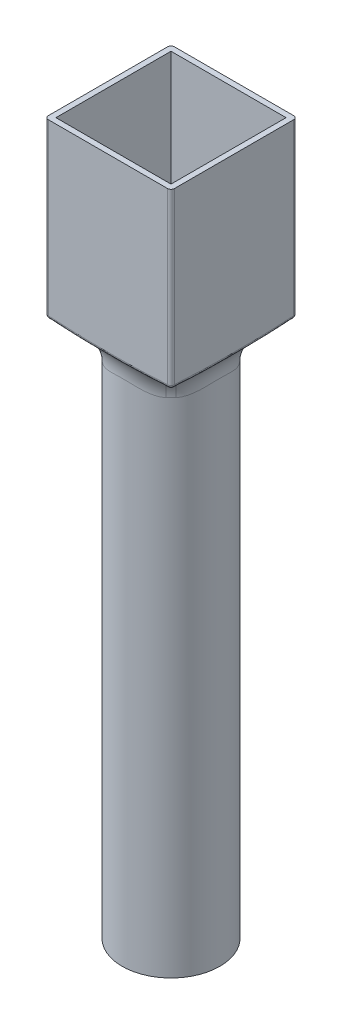
SolidWorks part; units mm, degrees
ref_plane "Спереди" through (0, 0, 0) normal (0, 0, 1) x (1, 0, 0)
ref_plane "Сверху" through (0, 0, 0) normal (0, 1, 0) x (1, 0, 0)
ref_plane "Справа" through (0, 0, 0) normal (1, 0, 0) x (0, 0, -1)
other "Configuration Table"
sketch "Эскиз1" plane through (0, 0, 0) normal (0, 1, 0) x (1, 0, 0)
  line L1 (-18.2, 18.2) -> (18.2, 18.2)
  line L2 (-18.2, 18.2) -> (-18.2, -18.2)
  line L3 (-18.2, -18.2) -> (18.2, -18.2)
  line L4 (18.2, 18.2) -> (18.2, -18.2)
  line L5 (0, -18.2) -> (0, 18.2) construction
  line L6 (-18.2, 0) -> (18.2, 0) construction
  line L7 (-16.6, 16.6) -> (16.6, 16.6)
  line L8 (-16.6, 16.6) -> (-16.6, -16.6)
  line L9 (-16.6, -16.6) -> (16.6, -16.6)
  line L10 (16.6, 16.6) -> (16.6, -16.6)
  line L11 (0, -16.6) -> (0, 16.6) construction
  line L12 (-16.6, 0) -> (16.6, 0) construction
  point P0 (0, 0)
  point P4 (0, 0)
  dimension "D1" = 36.4
  dimension "D2" = 33.2
extrude "Бобышка-Вытянуть1" add sketch "Эскиз1" along normal blind 48
sketch "Эскиз2" plane through (0, 0, 0) normal (0, -1, 0) x (1, 0, 0)
  line L1 (-18.2, -18.2) -> (18.2, -18.2)
  line L2 (-18.2, -18.2) -> (-18.2, 18.2)
  line L3 (-18.2, 18.2) -> (18.2, 18.2)
  line L4 (18.2, -18.2) -> (18.2, 18.2)
  line L5 (0, 18.2) -> (0, -18.2) construction
  line L6 (-18.2, 0) -> (18.2, 0) construction
  point P0 (0, 0)
extrude "Бобышка-Вытянуть2" add sketch "Эскиз2" along normal blind 2
sketch "Эскиз3" plane through (0, -2, 0) normal (0, -1, 0) x (1, 0, 0)
  circle A0 centre (0, 0) radius 14.1
  circle A1 centre (0, 0) radius 12.5
  dimension "D1" = 28.2
  dimension "D2" = 25
extrude "Бобышка-Вытянуть3" add sketch "Эскиз3" along normal blind 155
fillet "Скругление1" radius 10 1 edges at (0, -2, 14.1)
fillet "Скругление2" radius 10 1 edges at (0, -2, -12.5)
fillet "Скругление7" radius 1 4 edges at (18.2, 23, 18.2) (-18.2, 23, 18.2) (-18.2, 23, -18.2) (18.2, 23, -18.2)
fillet "Скругление8" radius 1 16 edges at (16.4989, -2, 18.2) (17.9071, -2, 17.9071) (18.2, -2, 16.4989) (18.2, -2, -16.4989) (17.9071, -2, -17.9071) (16.4989, -2, -18.2) (-16.4989, -2, -18.2) (-17.9071, -2, -17.9071) (-18.2, -2, -16.4989) (-18.2, -2, 16.4989) (-17.9071, -2, 17.9071) (-16.4989, -2, 18.2) (0, -2, -18.2) (18.2, -2, 0) (-18.2, -2, 0) (0, -2, 18.2)
fillet "Скругление9" radius 2 4 edges at (-16.6, 0, 0) (0, 0, -16.6) (0, 0, 16.6) (16.6, 0, 0)
sketch "Эскиз4" plane through (0, 0, 0) normal (0, 1, 0) x (1, 0, 0)
  circle A0 centre (0, 0) radius 8
  dimension "D1" = 16
extrude "Вырез-Вытянуть1" cut sketch "Эскиз4" against normal blind 15
fillet "Скругление10" radius 0.5 1 edges at (0, -157, -12.5)
